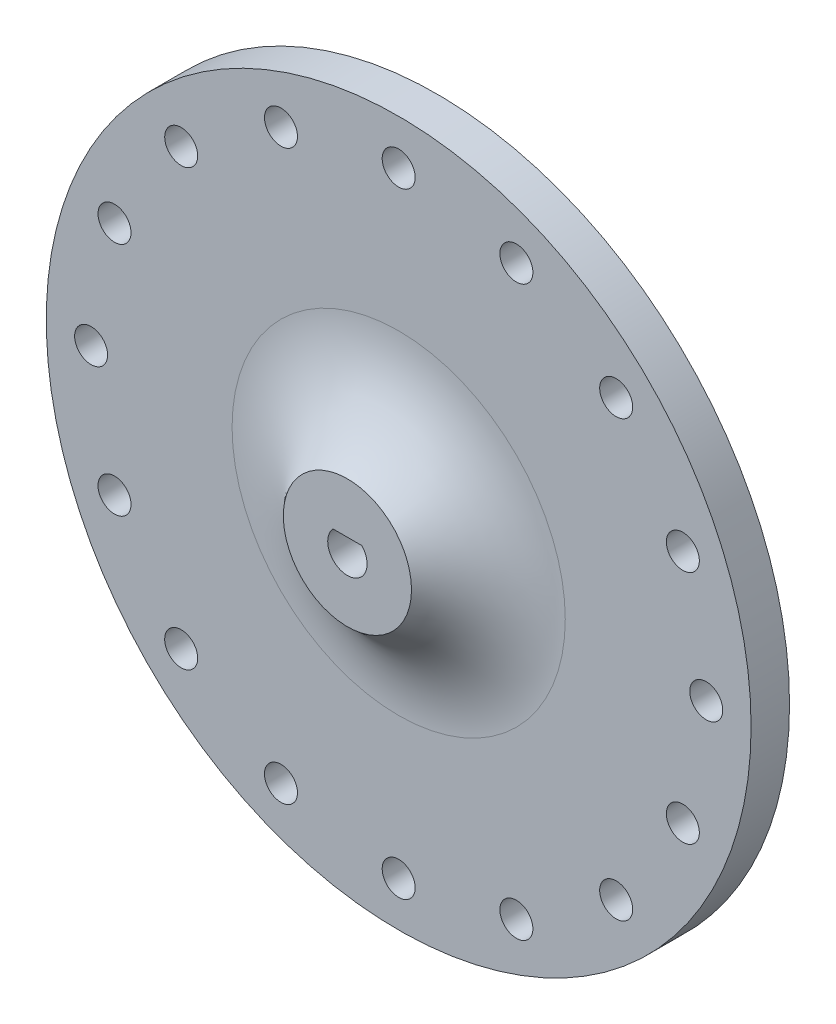
SolidWorks part; units mm, degrees
ref_plane "Plano frontal" through (0, 0, 0) normal (0, 0, 1) x (1, 0, 0)
ref_plane "Plano superior" through (0, 0, 0) normal (0, 1, 0) x (1, 0, 0)
ref_plane "Plano direito" through (0, 0, 0) normal (1, 0, 0) x (0, 0, -1)
sketch "Esboço1" plane through (0, 0, 0) normal (0, 0, 1) x (1, 0, 0)
  circle A0 centre (0, 0) radius 55
  dimension "D1" = 110
extrude "Ressalto-extrusão1" add sketch "Esboço1" along normal blind 6
sketch "Esboço2" plane through (0, 0, 6) normal (0, 0, 1) x (1, 0, 0)
  line L0 (-2.2462, 2.1) -> (2.2462, 2.1)
  line L1 (0, 0) -> (0, 2.1) construction
  arc A0 (-2.2462, 2.1) -> (2.2462, 2.1) centre (0, 0) ccw
  circle A1 centre (0, 0) radius 10
  dimension "D2" = 6.15
  dimension "D3" = 20
  dimension "D1" = 2.1
extrude "Ressalto-extrusão2" add sketch "Esboço2" along normal blind 8
fillet "Filete3" radius 20 1 edges at (10, 0, 6)
sketch "Esboço3" plane through (0, 0, 6) normal (0, 0, 1) x (1, 0, 0)
  line L0 (0, 0) -> (0, 48)
  circle A0 centre (0, 48) radius 2.575
  dimension "D1" = 5.15
  dimension "D2" = 48
extrude "Corte-extrusão1" cut sketch "Esboço3" against normal through all contours A0 region at (1.7693, 46.2307, 6)
pattern_circular "PadrãoCircular1" count 16 over 360 about axis through (0, 0, 6) along (0, 0, -1) of "Corte-extrusão1"
sketch "Esboço4" plane through (0, 0, 6) normal (0, 0, 1) x (1, 0, 0)
  line L1 (2.2462, 2.1) -> (-2.2462, 2.1)
  line L2 (2.2462, 2.1) -> (-2.2462, 2.1)
  arc A1 (-2.2462, 2.1) -> (2.2462, 2.1) centre (0, 0) ccw
  arc A2 (-2.2462, 2.1) -> (2.2462, 2.1) centre (0, 0) ccw
  dimension "D1" = 0
extrude "Corte-extrusão2" cut sketch "Esboço4" against normal through all
